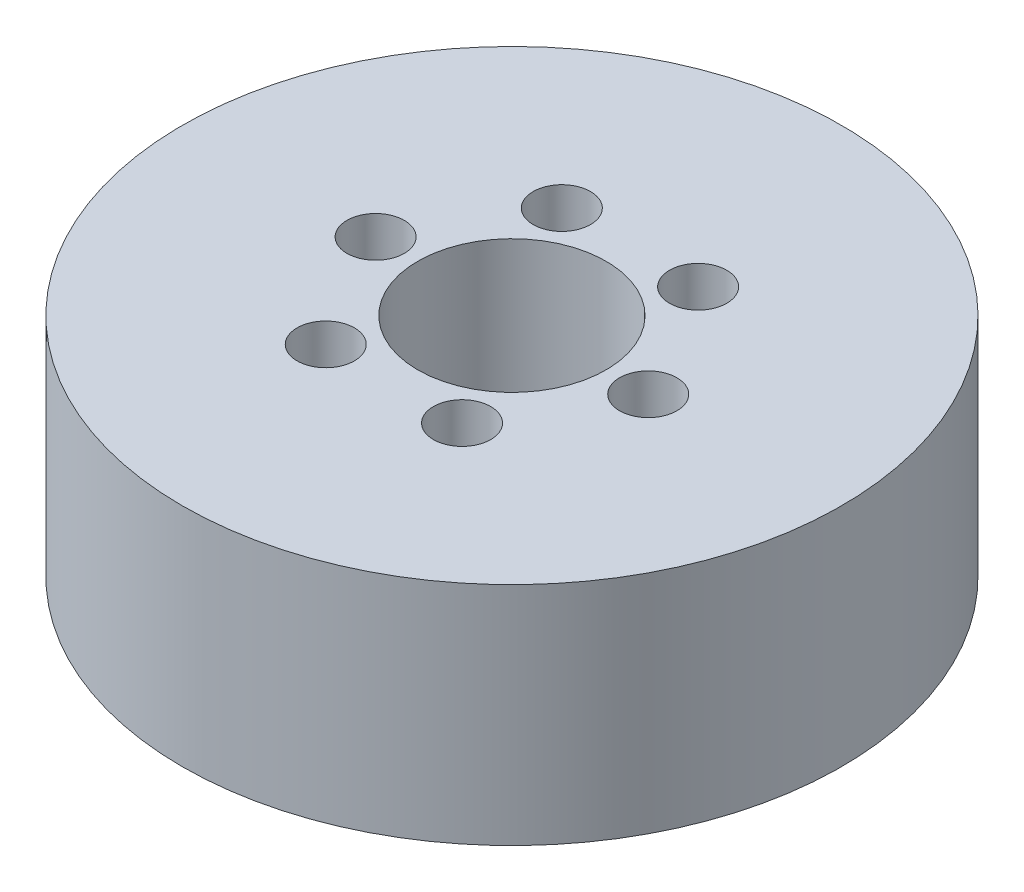
SolidWorks part; units mm, degrees
ref_plane "Front Plane" through (0, 0, 0) normal (0, 0, 1) x (1, 0, 0)
ref_plane "Top Plane" through (0, 0, 0) normal (0, 1, 0) x (1, 0, 0)
ref_plane "Right Plane" through (0, 0, 0) normal (1, 0, 0) x (0, 0, -1)
sketch "Sketch1" plane through (0, 0, 0) normal (0, 1, 0) x (1, 0, 0)
  circle A0 centre (0, 0) radius 17.5
  dimension "FLANGE_OD" = 35
extrude "Boss-Extrude1" add sketch "Sketch1" along normal blind 12
sketch "Sketch2" plane through (0, 0, 0) normal (0, 1, 0) x (1, 0, 0)
  circle A0 centre (0, 0) radius 5
  dimension "BORE_D" = 10
extrude "Cut-Extrude1" cut sketch "Sketch2" along normal through all
sketch "Sketch3" plane through (0, 12, 0) normal (0, 1, 0) x (1, 0, 0)
  circle A0 centre (0, 0) radius 7.2376 construction
  circle A1 centre (-7.2376, 0) radius 1.5217
  dimension "BOLT_D" = 3.0434
  dimension "BOLT_PCD" = 14.4751
extrude "Cut-Extrude2" cut sketch "Sketch3" against normal blind 10.7369
pattern_circular "CirPattern1" count 6 over 360 about axis through (0, 0, 0) along (0, 1, 0) of "Cut-Extrude2"
